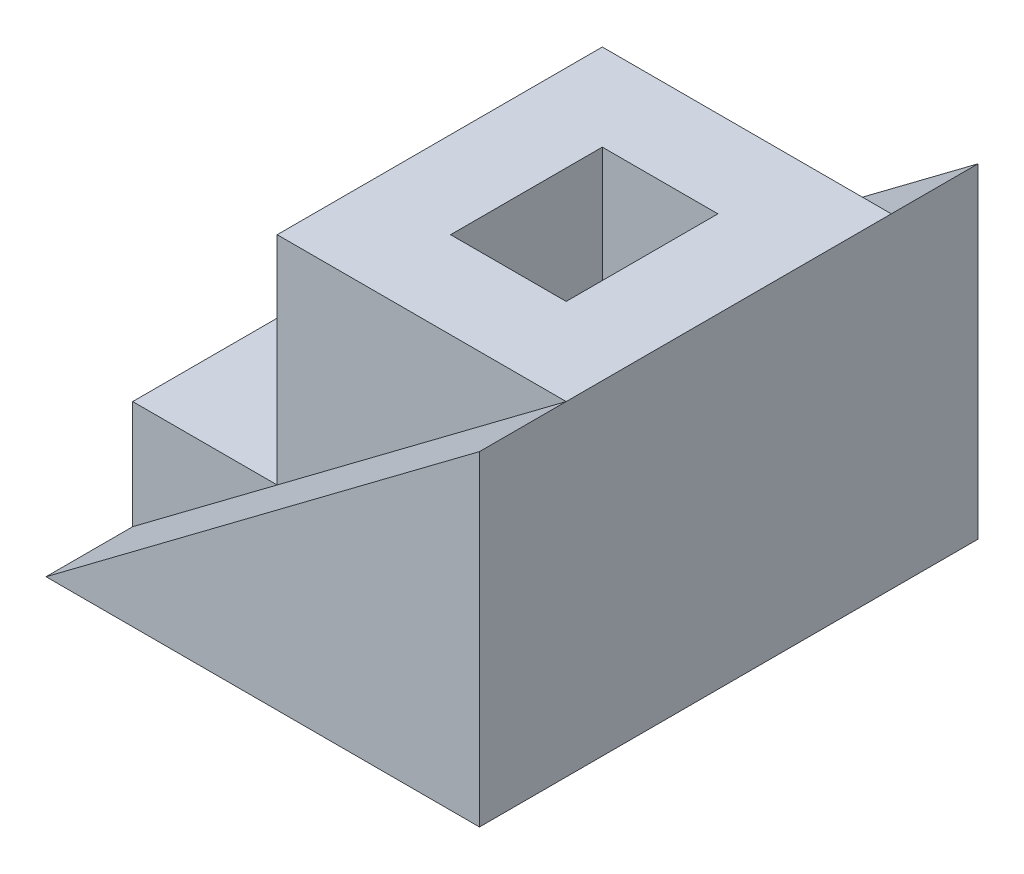
SolidWorks part; units mm, degrees
ref_plane "Спереди" through (0, 0, 0) normal (0, 0, 1) x (1, 0, 0)
ref_plane "Сверху" through (0, 0, 0) normal (0, 1, 0) x (1, 0, 0)
ref_plane "Справа" through (0, 0, 0) normal (1, 0, 0) x (0, 0, -1)
sketch "Эскиз1" plane through (0, 0, 0) normal (0, 0, 1) x (1, 0, 0)
  line L0 (-20, -5) -> (-6.6667, -5)
  line L1 (-20, -15) -> (20, -15)
  line L2 (-20, -15) -> (-20, 15)
  line L3 (-20, 15) -> (20, 15)
  line L4 (20, -15) -> (20, 15)
  line L5 (-20, -15) -> (20, 15) construction
  line L6 (-20, 15) -> (20, -15) construction
  line L7 (-6.6667, -5) -> (-6.6667, 15)
  point P0 (0, 0)
  dimension "D1" = 40
  dimension "D2" = 30
  dimension "D3" = 10
extrude "Бобышка-Вытянуть1" add sketch "Эскиз1" along normal blind 15 and the other way blind 15 contours L7 L0 L2 L1 L4 L3 region at (3.8095, -1.4286, 0)
sketch "Эскиз2" plane through (0, 0, 15) normal (0, 0, 1) x (1, 0, 0)
  line L0 (-20, -15) -> (20, 15)
  line L1 (20, 15) -> (20, -15)
  line L2 (20, -15) -> (-20, -15)
extrude "Бобышка-Вытянуть2" add sketch "Эскиз2" along normal blind 8
mirror "Зеркальное отражение1" about plane through (0, 0, 0) normal (0, 0, 1) of "Бобышка-Вытянуть2"
sketch "Эскиз3" plane through (0, 15, 0) normal (0, 1, 0) x (1, 0, 0)
  line L16 (1.3333, -7) -> (12, -7)
  line L17 (1.3333, 7) -> (1.3333, -7)
  line L18 (12, 7) -> (1.3333, 7)
  line L19 (12, -7) -> (12, 7)
  line L20 (1.3333, -7) -> (12, -7)
  line L21 (1.3333, 7) -> (1.3333, -7)
  line L22 (12, 7) -> (1.3333, 7)
  line L23 (12, -7) -> (12, 7)
  dimension "D1" = 8
extrude "Вырез-Вытянуть1" cut sketch "Эскиз3" against normal through all
